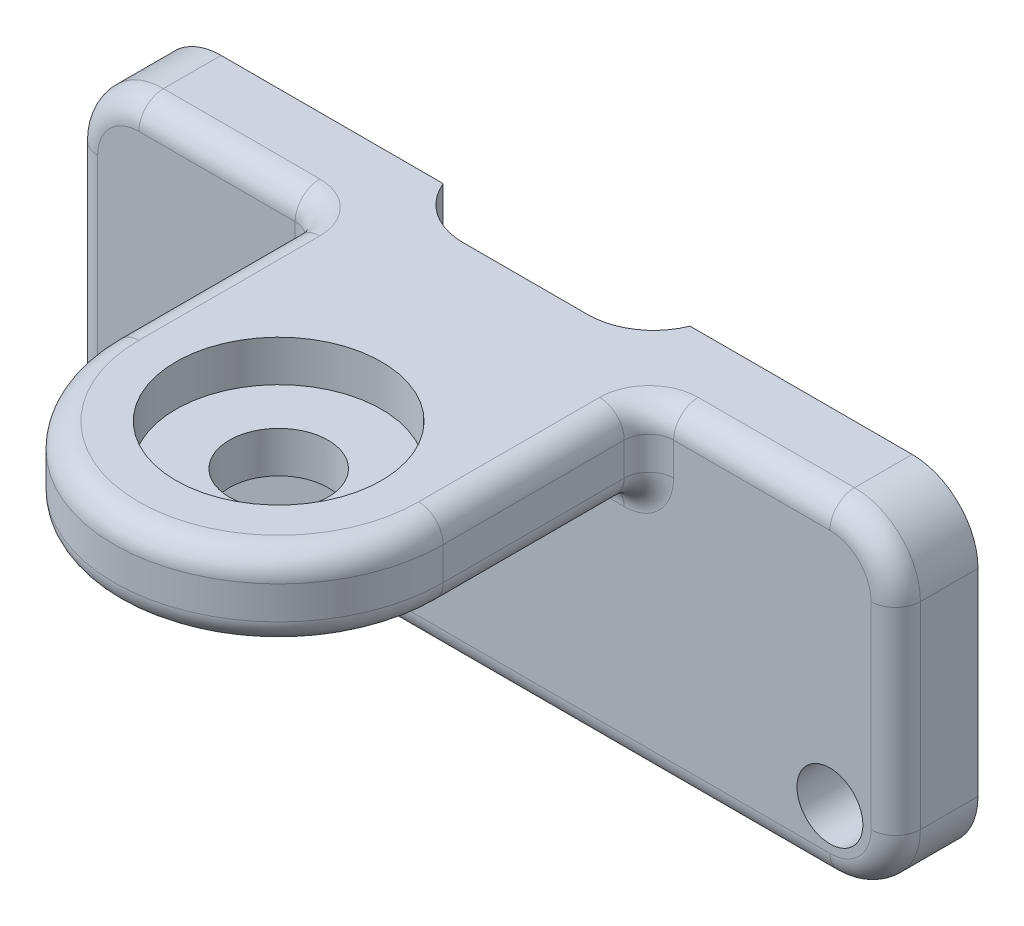
SolidWorks part; units mm, degrees
ref_plane "Спереди" through (0, 0, 0) normal (0, 0, 1) x (1, 0, 0)
ref_plane "Сверху" through (0, 0, 0) normal (0, 1, 0) x (1, 0, 0)
ref_plane "Справа" through (0, 0, 0) normal (1, 0, 0) x (0, 0, -1)
sketch "Эскиз1" plane through (0, 0, 0) normal (0, 0, 1) x (1, 0, 0)
  line L1 (-50, -20) -> (50, -20)
  line L2 (-50, -20) -> (-50, 20)
  line L3 (-50, 20) -> (50, 20)
  line L4 (50, -20) -> (50, 20)
  line L5 (-50, -20) -> (50, 20) construction
  line L6 (-50, 20) -> (50, -20) construction
  point P0 (0, 0)
  point P5 (0, 0)
  point P6 (0, 0)
  dimension "D1" = 40
  dimension "D2" = 100
extrude "Бобышка-Вытянуть1" add sketch "Эскиз1" along normal blind 10
sketch "Эскиз2" plane through (0, 20, 0) normal (0, 1, 0) x (1, 0, 0)
  line L0 (0, 0) -> (0, -36.742) construction
  line L1 (50, 0) -> (-50, 0) construction
  line L2 (20, -35) -> (20, 0)
  line L3 (-20, -35) -> (-20, 0)
  line L4 (20, 0) -> (-20, 0)
  arc A0 (20, -35) -> (-20, -35) centre (0, -35) cw
  dimension "D1" = 20
  dimension "D2" = 35
extrude "Бобышка-Вытянуть2" add sketch "Эскиз2" against normal blind 10
sketch "Эскиз5" plane through (0, 20, 0) normal (0, 1, 0) x (1, 0, 0)
  circle A0 centre (0, -35) radius 12.5
  dimension "D1" = 25
extrude "Вырез-Вытянуть1" cut sketch "Эскиз5" against normal blind 5
sketch "Эскиз6" plane through (0, 15, 0) normal (0, 1, 0) x (1, 0, 0)
  circle A0 centre (0, -35) radius 6
  dimension "D1" = 12
extrude "Вырез-Вытянуть2" cut sketch "Эскиз6" against normal through all
sketch "Эскиз7" plane through (0, 20, 0) normal (0, 1, 0) x (1, 0, 0)
  line L0 (50, 0) -> (-50, 0) construction
  line L1 (15, 0) -> (-15, 0)
  line L2 (15, 0) -> (15, -5)
  line L3 (15, -5) -> (-15, -5)
  line L4 (-15, 0) -> (-15, -5)
  point P6 (0, 0)
  point P8 (0, 0)
  dimension "D1" = 30
  dimension "D2" = 5
  dimension "D3" = 35
extrude "Вырез-Вытянуть3" cut sketch "Эскиз7" against normal through all
sketch "Эскиз8" plane through (0, 0, 10) normal (0, 0, 1) x (1, 0, 0)
  line L0 (0, 0) -> (0, -35.4239) construction
  line L1 (-50, -20) -> (50, -20) construction
  line L2 (-50, 20) -> (-50, -20) construction
  circle A0 centre (-42, -12) radius 4
  circle A1 centre (42, -12) radius 4
  dimension "D1" = 8
  dimension "D2" = 8
  dimension "D3" = 8
extrude "Вырез-Вытянуть4" cut sketch "Эскиз8" against normal through all
cosmetic thread "Условное изображение резьбы1" parameters "D1"=5, "D2"=9
cosmetic thread "Условное изображение резьбы2" parameters "D1"=5, "D2"=9
fillet "Скругление1" radius 8 6 edges at (50, -20, 5) (50, 20, 5) (-50, -20, 5) (-50, 20, 5) (-15, 0, 5) (15, 0, 5)
fillet "Скругление4" radius 3 18 edges at (0, 20, 55) (20, 20, 22.5) (-20, 20, 22.5) (-20, 15, 10) (-31, 20, 10) (-20, 10, 22.5) (0, 10, 55) (20, 10, 22.5) (0, 10, 10) (20, 15, 10) (31, 20, 10) (47.6569, 17.6569, 10) (50, 0, 10) (47.6569, -17.6569, 10) (-47.6569, 17.6569, 10) (-50, 0, 10) (-47.6569, -17.6569, 10) (0, -20, 10)
